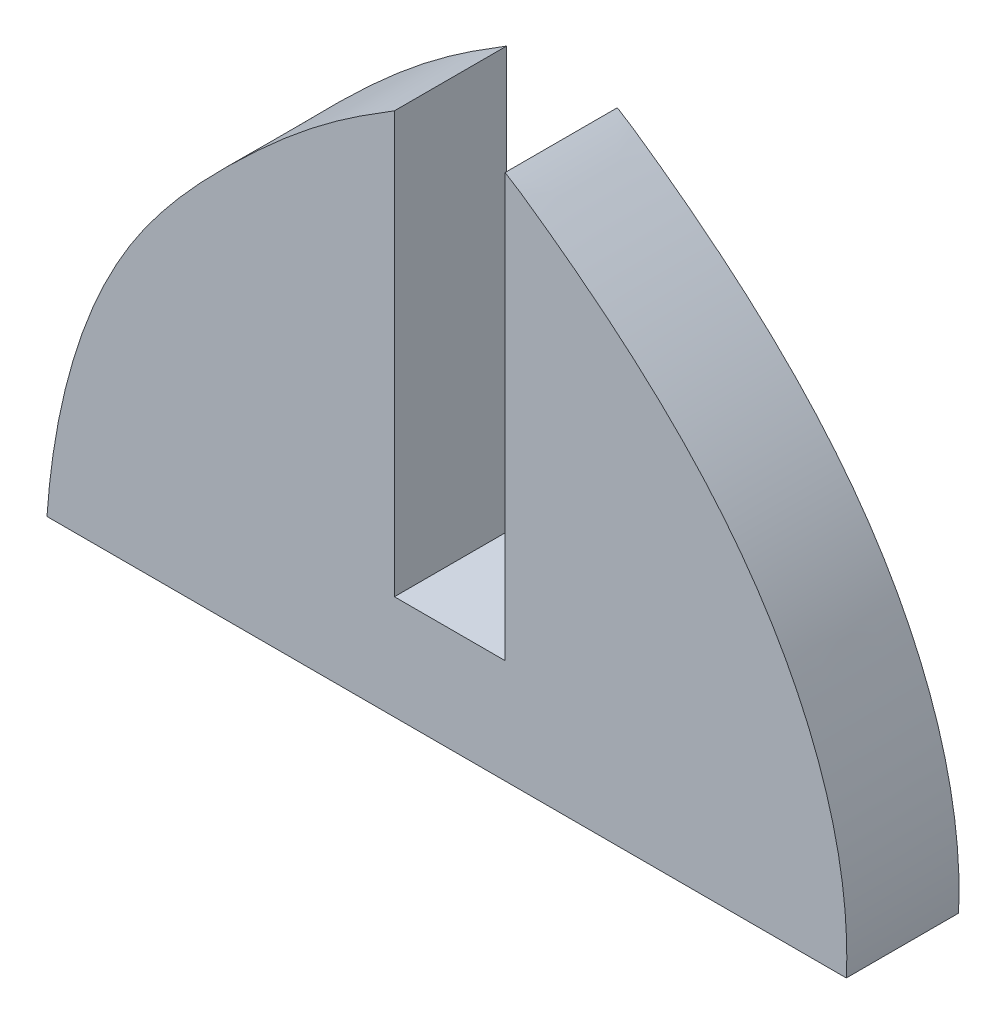
SolidWorks part; units mm, degrees
ref_plane "前视基准面" through (0, 0, 0) normal (0, 0, 1) x (1, 0, 0)
ref_plane "上视基准面" through (0, 0, 0) normal (0, 1, 0) x (1, 0, 0)
ref_plane "右视基准面" through (0, 0, 0) normal (1, 0, 0) x (0, 0, -1)
other "Configuration Table"
sketch "草图1" plane through (0, 0, 0) normal (0, 0, 1) x (1, 0, 0)
  line L0 (157.4101, 256.0211) -> (779.9201, 256.0211) construction
  line L1 (227.8199, 597.9035) -> (1733.8199, 597.9035) construction
  line L2 (376.5, 617) -> (1882.5, 617) construction
  line L6 (1180.2326, 162.9506) -> (1237.2119, 162.9506)
  line L7 (1208.8887, 170.3804) -> (1208.8887, 150.2319) construction
  line L8 (1205.0003, 200.3804) -> (1205.0003, 170.3804)
  line L11 (1205.0003, 171.7054) -> (1205.0003, 200.3804)
  line L13 (1205.0003, 170.3804) -> (1212.8887, 170.3804)
  line L14 (1212.8887, 170.3804) -> (1212.8887, 200.5148)
  spline S0 degree 3 poles (1212.8887, 200.5148) (1213.5918, 200.1027) (1216.3222, 198.2066) (1221.9149, 193.9644) (1232.596, 183.6254) (1237.638, 171.4915) (1237.2119, 162.9506) knots 0.03839 0.03839 0.03839 0.03839 0.088764 0.237953 0.477618 1 1 1 1
  spline S1 degree 3 poles (1205.0003, 200.3804) (1203.8021, 199.6441) (1199.6594, 197.0296) (1193.2768, 191.4389) (1183.5241, 180.8663) (1180.6944, 169.8063) (1180.2326, 162.9506) knots 0.038951 0.038951 0.038951 0.038951 0.12574 0.329523 0.570719 1 1 1 1
  dimension "D1" = 30.1344
extrude "凸台-拉伸1" add sketch "草图1" along normal blind 8 contours L8 S1 L6 S0 L14 L13 region at (1188.2, 184.431, 0)
